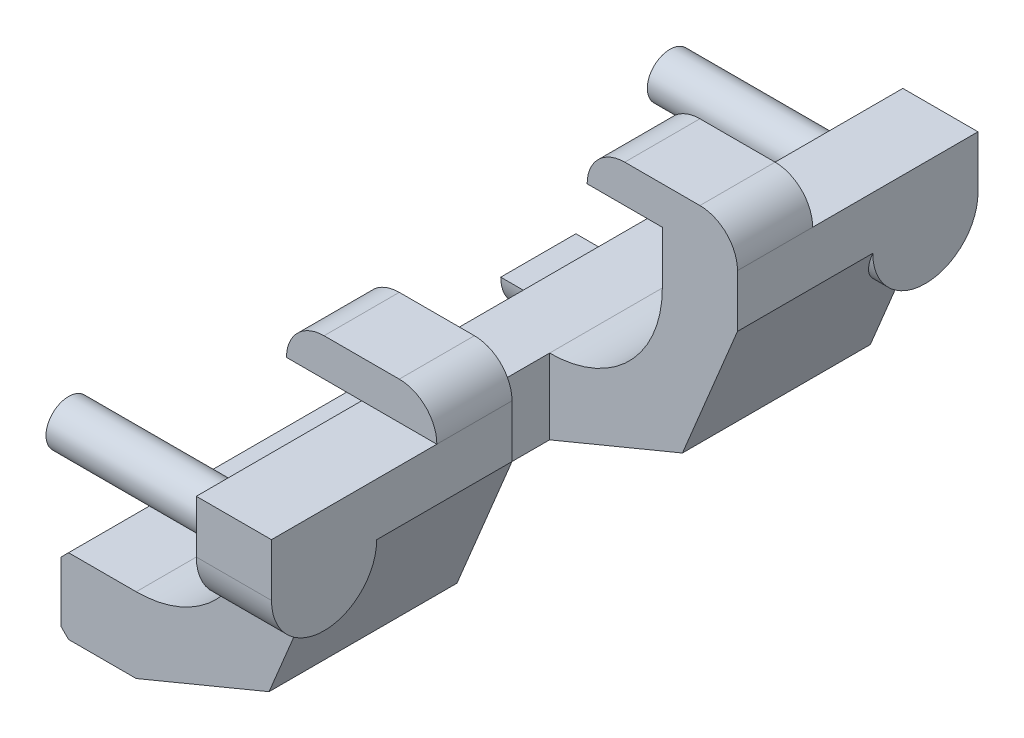
SolidWorks part; units mm, degrees
note: The reader was unsure of these and kept them because the rebuilt part matched: shared geometry of "Sketch5<3>", "Sketch8<4>".
material "ABS"
ref_plane "Front Plane" through (0, 0, 0) normal (0, 0, 1) x (1, 0, 0)
ref_plane "Top Plane" through (0, 0, 0) normal (0, 1, 0) x (1, 0, 0)
ref_plane "Right Plane" through (0, 0, 0) normal (1, 0, 0) x (0, 0, -1)
sketch "Sketch3" plane through (0, 0, 0) normal (1, 0, 0) x (0, 0, -1)
  line L0 (-55, 7) -> (-55, 13.488) construction
  line L1 (-55, 13.488) -> (-15, 13.488) construction
  line L2 (0, 0) -> (0, -7) construction
  line L3 (-55, 0) -> (55, 0)
  line L8 (-55, 0) -> (-55, 7)
  line L9 (-55, 7) -> (55, 7)
  line L10 (55, 0) -> (55, 7)
  line L11 (-15, 7) -> (-15, 0)
  line L12 (55, 7) -> (55, 13.488) construction
  line L13 (55, 13.488) -> (15, 13.488) construction
  line L14 (15, 7) -> (15, 0)
  line L15 (-47, 0) -> (-47, 7)
  line L16 (47, 0) -> (47, 7)
  arc A1 (-47, 0) -> (-33, 0) centre (-40, 0) ccw
  arc A2 (47, 0) -> (33, 0) centre (40, 0) cw
extrude "Boss-Extrude1" add sketch "Sketch3" along normal blind 10 contours L3 A1 | A2 L3 | L11 L9 L8 L3 | L9 L14 L3 L10
sketch "Sketch5" plane through (0, 0, -47) normal (0, 0, -1) x (-1, 0, 0)
  line L0 (-10, 0) -> (0, 0)
  line L1 (-10, 0) -> (-2.6777, -17.6777)
  line L2 (-2.6777, -17.6777) -> (15, -25)
  line L9 (-2.6777, 17.6777) -> (-10, 0) [skipped]
  line L10 (15, 25) -> (-2.6777, 17.6777) [skipped]
  line L11 (32.6777, 17.6777) -> (15, 25) [skipped]
  line L12 (40, 0) -> (32.6777, 17.6777) [skipped]
  line L13 (32.6777, -17.6777) -> (40, 0) [skipped]
  line L14 (15, -25) -> (32.6777, -17.6777) [skipped]
  line L15 (15, -15) -> (15, -25)
  arc A0 (0, 0) -> (15, -15) centre (15, 0) ccw
extrude "Boss-Extrude2" add sketch "Sketch5" against normal blind 80 from offset 7 offset against normal yes
sketch "Sketch6" plane through (0, 0, 0) normal (-1, 0, 0) x (0, 0, 1)
  line L1 (-47, 0) -> (-33, 0)
  line L2 (33, 0) -> (47, 0)
  line L3 (-40, 0) -> (-40, -7)
  line L4 (40, 0) -> (40, -7)
  arc A0 (-47, 0) -> (-33, 0) centre (-40, 0) ccw
  arc A1 (33, 0) -> (47, 0) centre (40, 0) ccw
extrude "Cut-Extrude1" cut sketch "Sketch6" along normal blind 2
sketch "Sketch7" plane through (0, 0, 0) normal (-1, 0, 0) x (0, 0, 1)
  circle A0 centre (-40, 0) radius 3
  circle A1 centre (40, 0) radius 3
sketch "Sketch9" plane through (-15, 0, 0) normal (-1, 0, 0) x (0, 0, 1)
  line L1 (-40, -15) -> (40, -15)
  line L2 (-40, -15) -> (-40, -25)
  line L3 (-40, -25) -> (40, -25)
  line L4 (40, -15) -> (40, -25)
extrude "Boss-Extrude4" add sketch "Sketch9" along normal blind 10
sketch "Sketch10" plane through (0, 0, -40) normal (0, 0, -1) x (-1, 0, 0)
  line L0 (25, -15) -> (24, -15)
  line L1 (25, -15) -> (15, -15) construction
  line L2 (24, -15) -> (25, -16)
  line L3 (25, -15) -> (25, -25) construction
  line L4 (25, -16) -> (25, -15)
  line L5 (25, -25) -> (24, -25)
  line L6 (25, -25) -> (15, -25) construction
  line L7 (24, -25) -> (25, -24)
  line L8 (25, -24) -> (25, -25)
extrude "Cut-Extrude3" cut sketch "Sketch10" against normal up to next (80 mm away)
extrude "Cut-Extrude4" cut sketch "Sketch5<3>" against normal blind 30 from surface at -32
sketch "Sketch5<3>" plane through (0, 0, -47) normal (0, 0, -1) x (-1, 0, 0) same geometry as "Sketch5"
extrude "Boss-Extrude5" add sketch "Sketch7" along normal blind 24
sketch "Sketch11" plane through (0, 0, -15) normal (0, 0, 1) x (1, 0, 0)
  line L1 (0, 7) -> (0, 0) construction
  line L2 (0, 7) -> (-10, 7)
  line L3 (-10, 7) -> (-10, 12)
  line L4 (-10, 12) -> (10, 12)
  line L7 (0, 7) -> (0, 10.3223) construction
  line L8 (0, 7) -> (10, 7)
  arc A0 (-10, 7) -> (-5, 12) centre (-5, 7) cw
  arc A1 (10, 7) -> (5, 12) centre (5, 7) ccw
extrude "Boss-Extrude6" add sketch "Sketch11" against normal blind 10
sketch "Sketch13" plane through (0, 0, 15) normal (0, 0, 1) x (1, 0, 0)
  line L2 (0, 7) -> (-10, 7)
  line L3 (-10, 7) -> (-10, 12)
  line L4 (-10, 12) -> (10, 12)
  line L7 (0, 7) -> (0, 10.3223) construction
  line L8 (0, 7) -> (10, 7)
  arc A0 (-10, 7) -> (-5, 12) centre (-5, 7) cw
  arc A1 (10, 7) -> (5, 12) centre (5, 7) ccw
extrude "Boss-Extrude8" add sketch "Sketch13" along normal blind 10
sketch "Sketch8" plane through (-25, 0, 0) normal (-1, 0, 0) x (0, 0, 1)
  line L0 (-32.5, -17) -> (-22.5, -17)
  line L4 (22.5, -17) -> (33.6648, -17)
  arc A1 (-32.5, -17) -> (-22.5, -17) centre (-27.5, -17) ccw
  arc A2 (32.5, -17) -> (22.5, -17) centre (27.5, -17) cw
  point P1 (0, 0)
extrude "Boss-Extrude3" add sketch "Sketch8" along normal blind 4 contours L0 A1
extrude "Cut-Extrude5" cut sketch "Sketch8<4>" against normal blind 4 contours A2 L4
sketch "Sketch8<4>" plane through (-25, 0, 0) normal (-1, 0, 0) x (0, 0, 1) same geometry as "Sketch8"
